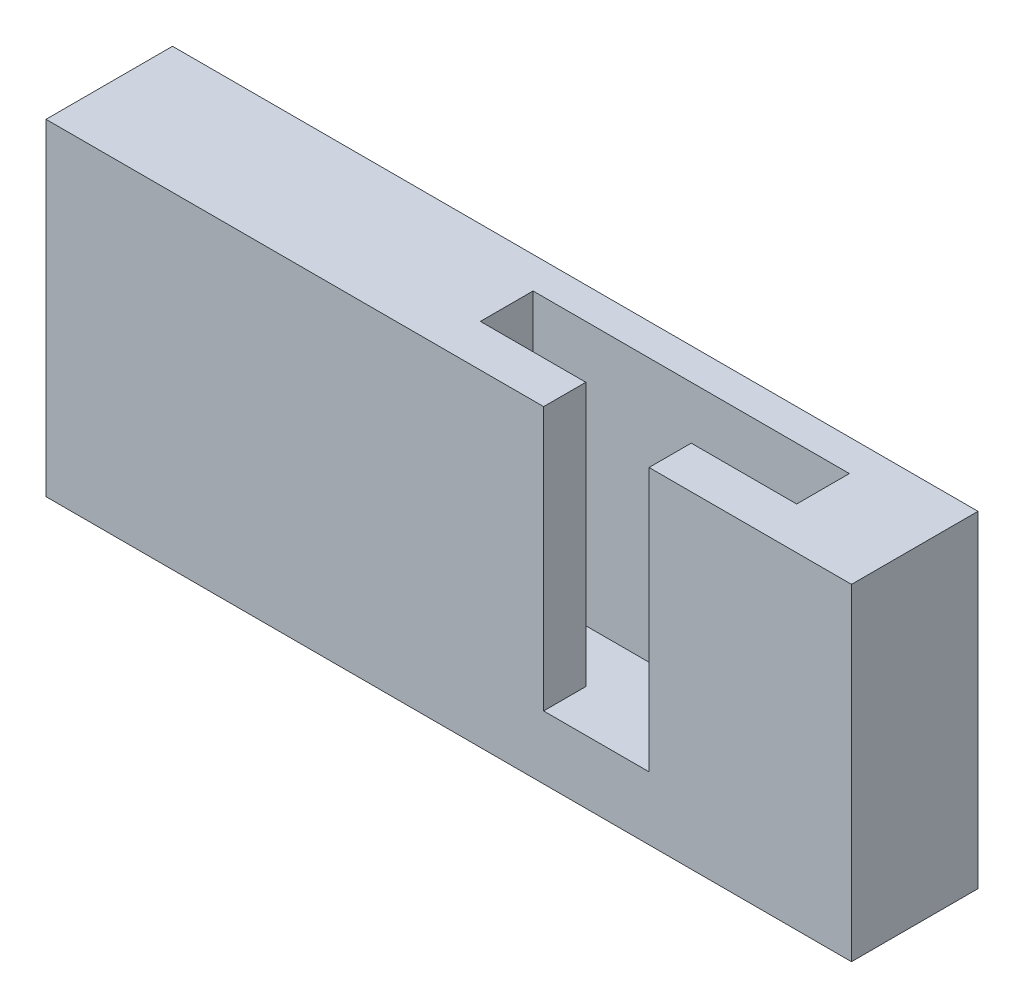
SolidWorks part; units mm, degrees
ref_plane "Front Plane" through (0, 0, 0) normal (0, 0, 1) x (1, 0, 0)
ref_plane "Top Plane" through (0, 0, 0) normal (0, 1, 0) x (1, 0, 0)
ref_plane "Right Plane" through (0, 0, 0) normal (1, 0, 0) x (0, 0, -1)
sketch "Sketch2" plane through (0, 0, 0) normal (0, 0, 1) x (1, 0, 0)
  line L1 (0, 0) -> (39, 0)
  line L2 (0, 0) -> (0, 15.5)
  line L3 (0, 15.5) -> (39, 15.5)
  line L4 (39, 0) -> (39, 15.5)
  dimension "D1" = 15.5
  dimension "D2" = 39
extrude "Boss-Extrude1" add sketch "Sketch2" against normal blind 6
sketch "Sketch3" plane through (0, 15.5, 0) normal (0, 1, 0) x (1, 0, 0)
  line L0 (24, 0) -> (24, 2)
  line L1 (39, 0) -> (0, 0) construction
  line L2 (24, 2) -> (19, 2)
  line L3 (19, 2) -> (19, 4.5)
  line L4 (19, 4.5) -> (34, 4.5)
  line L5 (34, 4.5) -> (34, 2)
  line L6 (34, 2) -> (29, 2)
  line L7 (29, 2) -> (29, 0)
  line L8 (29, 0) -> (24, 0)
  line L10 (39, 6) -> (39, 0) construction
  dimension "D1" = 2
  dimension "D2" = 2.5
  dimension "D3" = 2
  dimension "D4" = 5
  dimension "D5" = 5
  dimension "D6" = 5
  dimension "D7" = 10
extrude "Cut-Extrude1" cut sketch "Sketch3" against normal offset from surface (12.5 mm away) 3 up to face at (19.5, 0, -3)
sketch "Sketch4" plane through (39, 0, 0) normal (1, 0, 0) x (0, 0, -1)
  line L1 (-3.505, 19.2954) -> (16.8149, 19.2954)
  line L2 (-3.505, 19.2954) -> (-3.505, -8.9413)
  line L3 (-3.505, -8.9413) -> (16.8149, -8.9413)
  line L4 (16.8149, 19.2954) -> (16.8149, -8.9413)
extrude "Cut-Extrude2" cut sketch "Sketch4" against normal blind 0.4
sketch "Sketch5" plane through (0, 0, 0) normal (-1, 0, 0) x (0, 0, 1)
  line L1 (-8.1129, 18.4267) -> (2.9706, 18.4267)
  line L2 (-8.1129, 18.4267) -> (-8.1129, -4.1582)
  line L3 (-8.1129, -4.1582) -> (2.9706, -4.1582)
  line L4 (2.9706, 18.4267) -> (2.9706, -4.1582)
extrude "Cut-Extrude3" cut sketch "Sketch5" against normal blind 0.4
